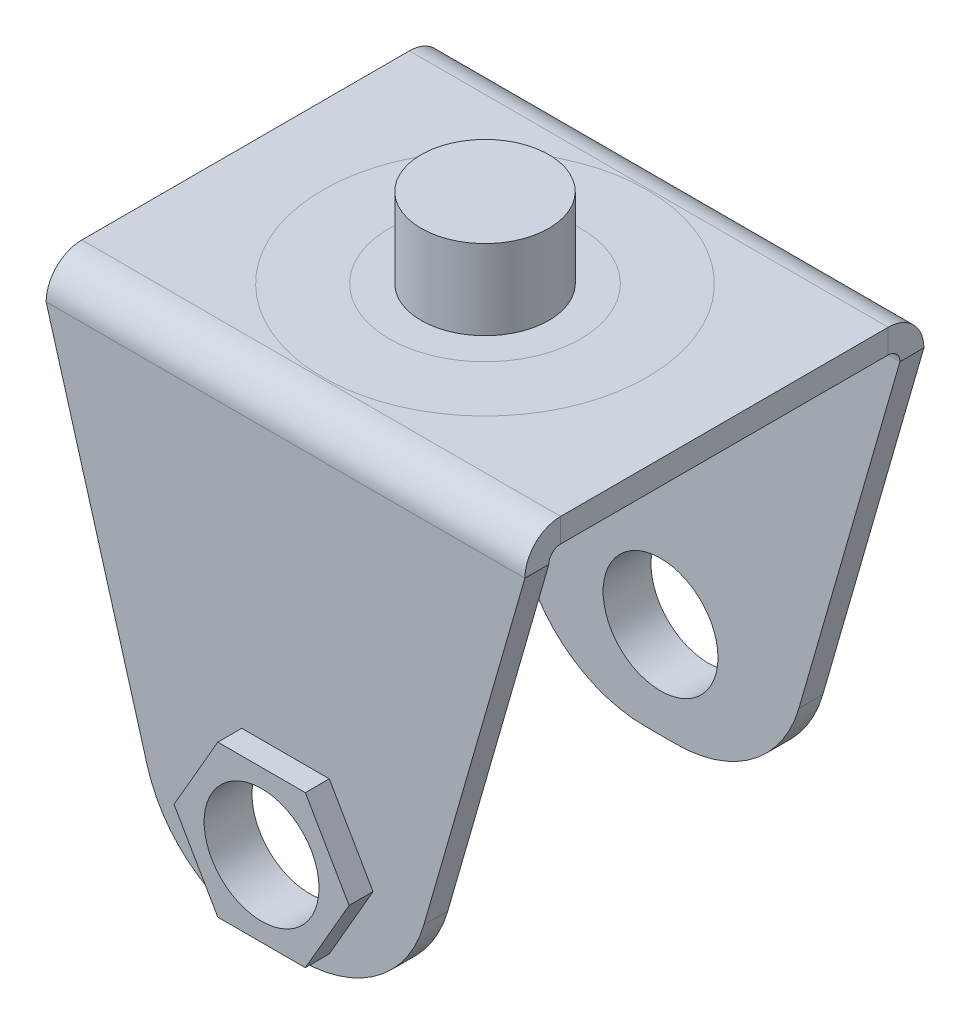
SolidWorks part; units mm, degrees
note: The reader was unsure of these and kept them because the rebuilt part matched: flange length of "Edge-Flange1".
ref_plane "Front Plane" through (0, 0, 0) normal (0, 0, 1) x (1, 0, 0)
ref_plane "Top Plane" through (0, 0, 0) normal (0, 1, 0) x (1, 0, 0)
ref_plane "Right Plane" through (0, 0, 0) normal (1, 0, 0) x (0, 0, -1)
sketch "Sketch1" plane through (0, 0, 0) normal (0, 1, 0) x (1, 0, 0)
  line L1 (-15, -11) -> (15, -11)
  line L2 (-15, -11) -> (-15, 11)
  line L3 (-15, 11) -> (15, 11)
  line L4 (15, -11) -> (15, 11)
  line L5 (-15, -11) -> (15, 11) construction
  line L6 (-15, 11) -> (15, -11) construction
  point P0 (0, 0)
  dimension "D1" = 22
  dimension "D2" = 30
sheet metal parameters "Sheet-Metal1" thickness 1.5 parameters "D1"=0.7366
base flange "Base-Flange1" sketch "Sketch1" thickness 1.5 reverse thickness direction no parameters "D1"=0.7366
edge flange "Edge-Flange1" sketch "Sketch9" flange profiles "Sketch9", "Sketch10" flange angle 90 flange length 30 flange position material outside bend radius 0.7366 thickness 1.5 relief rectangular parameters "D6"=10, "D8"=1
sketch "Sketch9" plane through (0, -1.5, 11) normal (0, 0, 1) x (-1, 0, 0)
  line L0 (15, 0) -> (-15, 0) construction
  line L1 (15, 0) -> (-15, 0)
  line L2 (-15, 0) -> (-15, 28.5)
  line L3 (-15, 28.5) -> (15, 28.5)
  line L4 (15, 28.5) -> (15, 0)
sketch "Sketch10" plane through (0, -1.5, -11) normal (0, 0, -1) x (1, 0, 0)
  line L0 (15, 0) -> (-15, 0) construction
  line L1 (15, 0) -> (-15, 0)
  line L2 (-15, 0) -> (-15, 28.5)
  line L3 (-15, 28.5) -> (15, 28.5)
  line L4 (15, 28.5) -> (15, 0)
bend "EdgeBend1" bend radius 0.7366 bend angle 90 parameters "D5"=1
bend "EdgeBend2" bend radius 0.7366 bend angle 90 parameters "D5"=2
sketch "Sketch11" plane through (0, 0, 12.5) normal (0, 0, 1) x (1, 0, 0)
  line L0 (-15, -2.2366) -> (-7, -30)
  line L1 (-15, -30) -> (15, -30) construction
  line L2 (-7, -30) -> (-15, -30)
  line L3 (-15, -30) -> (-15, -2.2366)
  line L4 (15, -2.2366) -> (7, -30)
  line L5 (7, -30) -> (15, -30)
  line L6 (15, -30) -> (15, -2.2366)
  dimension "D1" = 8
  dimension "D2" = 8
extrude "Cut-Extrude1" cut sketch "Sketch11" against normal through all
fillet "Fillet1" radius 8 4 edges at (-7, -30, 11.75) (7, -30, 11.75) (-7, -30, -11.75) (7, -30, -11.75)
sketch "Sketch12" plane through (0, 0, 12.5) normal (0, 0, 1) x (1, 0, 0)
  line L0 (0, -30) -> (0, -24) construction
  line L1 (-0.9797, -30) -> (0.9797, -30) construction
  circle A0 centre (0, -24) radius 3.6
  dimension "D2" = 7.2
  dimension "D1" = 6
extrude "Cut-Extrude2" cut sketch "Sketch12" against normal through all
sketch "Sketch13" plane through (0, 0, 12.5) normal (0, 0, 1) x (1, 0, 0)
  line L1 (5.4848, -24) -> (2.7424, -19.25)
  line L2 (2.7424, -19.25) -> (-2.7424, -19.25)
  line L3 (-2.7424, -19.25) -> (-5.4848, -24)
  line L4 (-5.4848, -24) -> (-2.7424, -28.75)
  line L5 (-2.7424, -28.75) -> (2.7424, -28.75)
  line L6 (2.7424, -28.75) -> (5.4848, -24)
  circle A0 centre (0, -24) radius 3.6
  circle A1 centre (0, -24) radius 4.75 construction
  dimension "D1" = 9.5
extrude "Boss-Extrude1" add sketch "Sketch13" along normal blind 1.5
mirror "Mirror1" about plane through (0, 0, 0) normal (0, 0, 1) of "Boss-Extrude1"
sketch "Sketch14" plane through (0, 0, 0) normal (0, 1, 0) x (1, 0, 0)
  circle A0 centre (0, 0) radius 6
  dimension "D1" = 12
extrude "Boss-Extrude2" add sketch "Sketch14" along normal blind 1
sketch "Sketch15" plane through (0, 1, 0) normal (0, 1, 0) x (1, 0, 0)
  circle A0 centre (0, 0) radius 10
  dimension "D1" = 20
extrude "Boss-Extrude3" add sketch "Sketch15" along normal blind 4
fillet "Fillet2" radius 2 1 edges at (0, 1, 10)
sketch "Sketch16" plane through (0, 5, 0) normal (0, 1, 0) x (1, 0, 0)
  circle A0 centre (0, 0) radius 4
  dimension "D1" = 8
extrude "Boss-Extrude4" add sketch "Sketch16" along normal blind 5
sketch "Sketch17" plane through (0, 10, 0) normal (0, 1, 0) x (1, 0, 0)
  circle A0 centre (0, 0) radius 10.1638
  circle M2 centre (0, 0) radius 4
extrude "Cut-Extrude4" cut sketch "Sketch17" along direction (0, -1, 0) on the side against the normal blind 10 contours A0 M2 normal cut yes
sketch "Sketch18" plane through (0, 10, 0) normal (0, 1, 0) x (1, 0, 0)
  circle A0 centre (0, 0) radius 4
extrude "Cut-Extrude5" cut sketch "Sketch18" against normal blind 5 normal cut yes
flat pattern "Flat-Pattern1" [suppressed]
sketch "Bend-Lines1" plane through (0, 0, 0) normal (0, 1, 0) x (-1, 0, 0)
sketch3d "Bounding-Box1" [suppressed]
  line L0 (-22, 22, 0) -> (-22, 0, 0) construction
  line L1 (0, 22, 0) -> (0, 0, 0) construction
  line L2 (-22, 22, 0) -> (0, 22, 0) construction
  line L3 (-22, 0, 0) -> (0, 0, 0) construction
bend of the flat pattern "Flatten-<EdgeBend1>1"
bend of the flat pattern "Flatten-<EdgeBend2>1"
